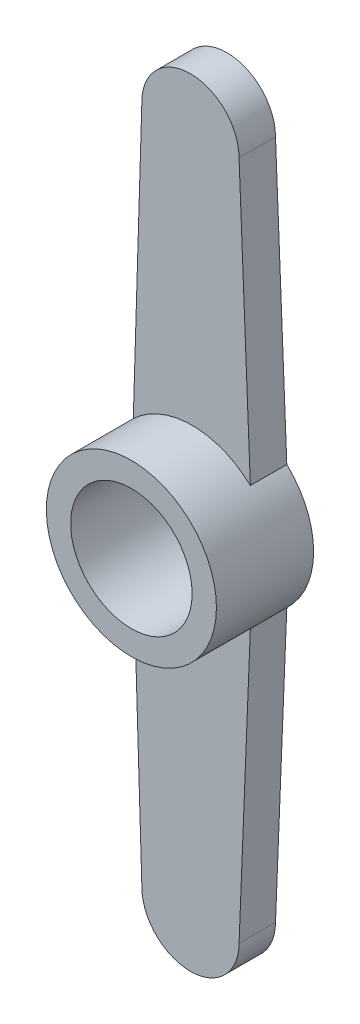
SolidWorks part; units mm, degrees
ref_plane "Plan de face" through (0, 0, 0) normal (0, 0, 1) x (1, 0, 0)
ref_plane "Plan de dessus" through (0, 0, 0) normal (0, 1, 0) x (1, 0, 0)
ref_plane "Plan de droite" through (0, 0, 0) normal (1, 0, 0) x (0, 0, -1)
sketch "Esquisse1" plane through (0, 0, 0) normal (0, 0, 1) x (1, 0, 0)
  line L0 (-2.5, 0) -> (-2.0685, 14)
  line L1 (-2.0685, 14) -> (1.9315, 14)
  line L2 (1.9315, 14) -> (2.5, 0)
  line L3 (-2.5, 0) -> (2.5, 0)
  line L4 (-2.5, 0) -> (-2.0685, -14)
  line L5 (1.9315, -14) -> (2.5, 0)
  circle A0 centre (0, 0) radius 3.5
  circle A1 centre (0, 0) radius 2.5
  circle A2 centre (-0.0685, 14) radius 2
  circle A3 centre (-0.0685, -14) radius 2
  dimension "D1" = 7
  dimension "D2" = 5
  dimension "D4" = 4
  dimension "D3" = 14
extrude "Boss.-Extru.1" add sketch "Esquisse1" along normal blind 4 contours A1 L2 A0 L0 | A1 L5 A0 L2 | A1 L4 A0 L5 | A1 L0 A0 L4 region at (-2.8823, 0, 0) region at (-0.0131, 2.5093, 0) region at (2.8746, 0, 0) region at (-0.0131, -2.5093, 0)
extrude "Boss.-Extru.2" add sketch "Esquisse1<3>" along normal blind 1.5 contours A2 L0 A0 L2 | L1 A2 | L1 A2 | L4 A3 L5 A0 | A3 region at (-0.0383, 7.7184, 0) region at (-0.0383, -7.7184, 0) region at (-0.0685, 14.8488, 0) region at (-0.0685, 13.1512, 0) region at (-0.0685, -14, 0)
sketch "Esquisse1<3>" plane through (0, 0, 0) normal (0, 0, 1) x (1, 0, 0) same geometry as "Esquisse1"
